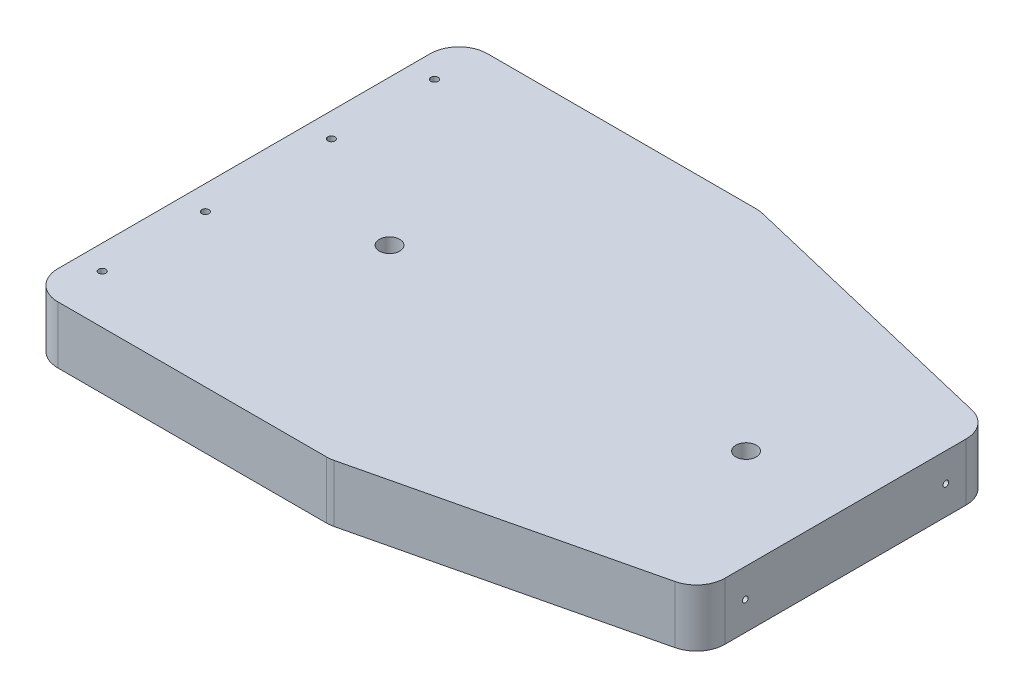
SolidWorks part; units mm, degrees
material "Carvalho"
ref_plane "Plano frontal" through (0, 0, 0) normal (0, 0, 1) x (1, 0, 0)
ref_plane "Plano superior" through (0, 0, 0) normal (0, 1, 0) x (1, 0, 0)
ref_plane "Plano direito" through (0, 0, 0) normal (1, 0, 0) x (0, 0, -1)
sketch "Esboço1" plane through (0, 0, 0) normal (0, 1, 0) x (1, 0, 0)
  line L0 (210, 50) -> (105, 75)
  line L1 (0, -75) -> (105, -75)
  line L2 (0, -75) -> (0, 75)
  line L3 (0, 75) -> (105, 75)
  line L4 (210, -50) -> (210, 50)
  line L5 (195, -38.5714) -> (210, -38.5714) construction
  line L6 (195, -38.5714) -> (195, -53.5714) construction
  line L7 (105, -75) -> (210, -50)
  line L8 (-14.8259, 0) -> (14.392, 0) construction
  line L9 (0, 21.2472) -> (0, -16.7598) construction
  circle A0 centre (50.8, 0) radius 3.5719
  circle A1 centre (175.26, 0) radius 3.57
  circle A2 centre (8.5, -58) radius 1.25
  circle A3 centre (8.5, -22) radius 1.25
  circle A4 centre (8.5, 22) radius 1.25
  circle A5 centre (8.5, 58) radius 1.25
  circle A6 centre (195, -38.5714) radius 0.5
  circle A7 centre (195, 38.5714) radius 0.5
  point P0 (0, 0)
  dimension "D3" = 7.1437
  dimension "D5" = 7.14
  dimension "D9" = 1
  dimension "D12" = 2.5
  dimension "D1" = 25
  dimension "D2" = 150
  dimension "D4" = 50.8
  dimension "D6" = 210
  dimension "D7" = 175.26
  dimension "D8" = 105
  dimension "D10" = 15
  dimension "D11" = 15
extrude "Ressalto-extrusão1" add sketch "Esboço1" along normal blind 15 and the other way blind 5 contours L1 L7 L4 L0 L3 L2 A0 A1 A2 A3 A4 A5 A6 A7 | A6 | A7 region at (98.6526, 0, 0)
sketch "Esboço2" plane through (210, 0, 0) normal (1, 0, 0) x (0, 0, -1)
  line L0 (0, -5) -> (0, 15) construction
  line L1 (-50, -5) -> (50, -5) construction
  line L2 (-50, 15) -> (50, 15) construction
  circle A0 centre (-35, 5) radius 1
  circle A1 centre (35, 5) radius 1
  point P8 (0, 5)
  dimension "D2" = 2
  dimension "D1" = 35
extrude "Corte-extrusão1" cut sketch "Esboço2" against normal blind 10
fillet "Filete1" radius 10 6 edges at (0, 5, 75) (105, 5, 75) (210, 5, 50) (210, 5, -50) (0, 5, -75) (105, 5, -75)
sketch "Esboço6" plane through (0, 15, 0) normal (0, 1, 0) x (1, 0, 0)
  line L0 (195, 38.1521) -> (195, -38.1521)
  line L2 (65, -60) -> (65, 60)
  line L4 (210, -42.1014) -> (210, 42.1014) construction
  line L5 (202.3162, 51.8295) -> (106.1421, 74.7281) construction
  line L8 (-4.1061, 0) -> (243.1802, 0) construction
  line L9 (65, 60) -> (103.2389, 60)
  line L10 (103.2389, 60) -> (195, 38.1521)
  line L11 (65, -60) -> (103.2389, -60)
  line L12 (103.2389, -60) -> (195, -38.1521)
  line L15 (175, -22.3549) -> (195, -17.593)
  line L16 (175, -42.914) -> (175, -22.3549)
  line L17 (103.8259, 75) -> (10, 75) construction
  line L18 (0, 65) -> (0, -65) construction
  line L19 (175, 22.3549) -> (195, 17.593)
  arc A0 (175, -22.3549) -> (175, 22.3549) centre (175.26, 0) cw
  circle A2 centre (175.26, 0) radius 3.57 construction
  point P24 (175, 22.3549)
  circle M45 centre (175.26, 0) radius 3.57
  dimension "D1" = 15
  dimension "D2" = 15
  dimension "D3" = 15
  dimension "D4" = 65
  dimension "D5" = 20
  dimension "D6" = 20
extrude "Corte-extrusão2" cut sketch "Esboço6" along normal blind 10 from surface contours L8 L2 L11 L12 L16 L15 L0 M45 | L2 L8 L0 L10 L9 M45 region at (118.3408, 15, -28.8599) region at (113.4465, 15, 28.7576) starting at face at (105.3184, -5, 0)
fillet "Filete2" radius 10 8 edges at (65, 0, 60) (65, 0, -60) (103.2389, 0, -60) (195, 0, -17.593) (175, 0, -22.3549) (175, 0, 22.3549) (175, 0, 42.914) (195, 0, -38.1521)
